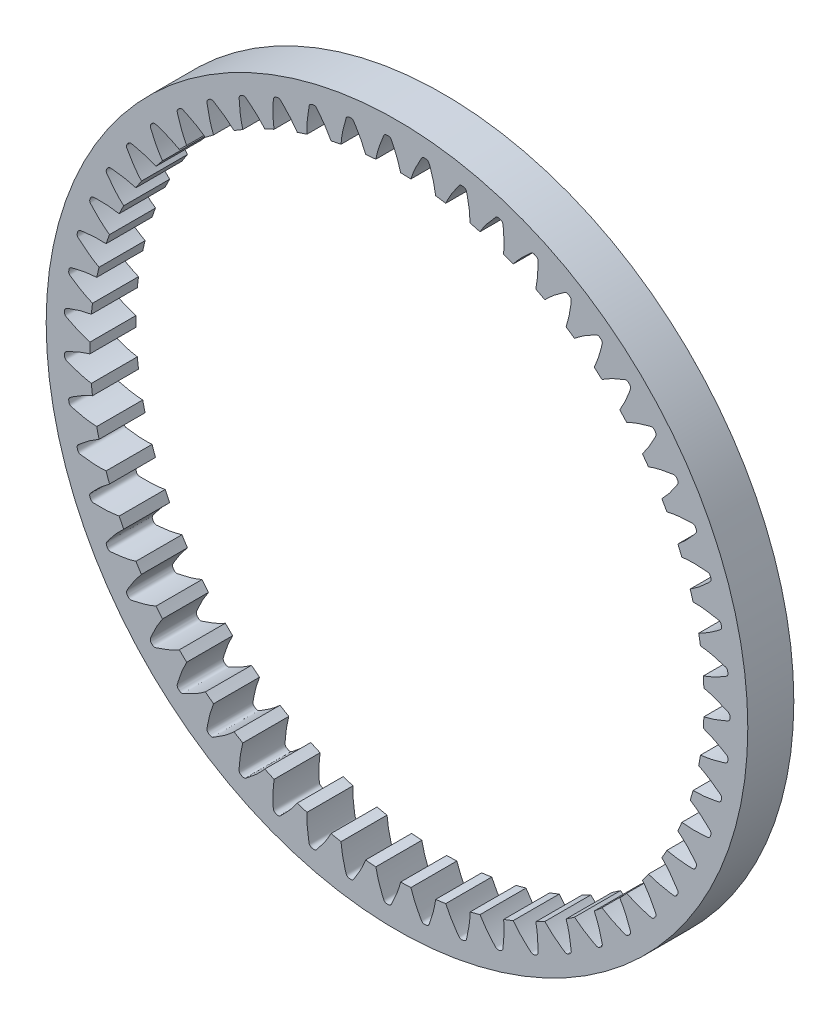
SolidWorks part; units mm, degrees
ref_plane "Front Plane" through (0, 0, 0) normal (0, 0, 1) x (1, 0, 0)
ref_plane "Top Plane" through (0, 0, 0) normal (0, 1, 0) x (1, 0, 0)
ref_plane "Right Plane" through (0, 0, 0) normal (1, 0, 0) x (0, 0, -1)
ref_axis "Axis1" through (0, 0, 55) along (0, 0, -1)
sketch "SketchRevolveSpurGear" plane through (0, 0, 0) normal (1, 0, 0) x (0, 0, -1)
  line L0 (0, 0) -> (1, 0) construction
  line L1 (-2, 26.7) -> (-2, 31.5)
  line L2 (-2, 31.5) -> (2, 31.5)
  line L3 (2, 31.5) -> (2, 26.7)
  line L4 (2, 26.7) -> (-2, 26.7)
  dimension "Side1" = 2
  dimension "OutsideRadius" = 31.5
  dimension "Side2" = 2
  dimension "MinorDiameter" = 53.4
revolve "SpurGear" add sketch "SketchRevolveSpurGear" angle 360 about L0
sketch "SketchToothSpurGear" plane through (0, 0, 0) normal (0, 0, 1) x (1, 0, 0)
  arc A0 (26.6611, -1.0844) -> (26.6611, 1.0844) centre (0, 0) ccw
  spline S0 degree 3 poles (26.6611, 1.0844) (26.7713, 1.0607) (26.9424, 1.0195) (27.1776, 0.9545) (27.373, 0.8955) (27.5803, 0.8276) (27.7992, 0.7503) (28.0292, 0.6628) (28.2705, 0.5652) (28.5213, 0.4543) (28.7068, 0.3744) (28.8169, 0.3155) (28.8506, 0.2891) (28.8801, 0.2588) (28.905, 0.2247) (28.9248, 0.1873) (28.9441, 0.1349) (28.9506, 0.0821) (28.9499, 0.0327) (28.9501, 0) (28.9499, -0.0327) (28.9506, -0.0821) (28.9441, -0.1349) (28.9248, -0.1873) (28.905, -0.2247) (28.8801, -0.2588) (28.8506, -0.2891) (28.8169, -0.3155) (28.7068, -0.3744) (28.5213, -0.4543) (28.2705, -0.5652) (28.0292, -0.6628) (27.7992, -0.7503) (27.5803, -0.8276) (27.373, -0.8955) (27.1776, -0.9545) (26.9424, -1.0195) (26.7713, -1.0607) (26.6611, -1.0844) knots 0 0 0 0 0.063683 0.099491 0.137943 0.17904 0.222781 0.269167 0.318197 0.369871 0.42419 0.432384 0.440322 0.448261 0.456199 0.464138 0.472077 0.487661 0.493831 0.5 0.506169 0.512339 0.527923 0.535862 0.543801 0.551739 0.559678 0.567616 0.57581 0.630129 0.681803 0.730833 0.777219 0.82096 0.862057 0.900509 0.936317 1 1 1 1
extrude "ToothExtrudeCutSpurGear" cut sketch "SketchToothSpurGear" against normal blind 2 and the other way blind 2
pattern_circular "PatternSpurGear" count 55 every 6.545 about axis through (0, 0, 55) along (0, 0, -1) of "ToothExtrudeCutSpurGear"
sketch "AuxiliarySketchSpurGear" plane through (0, 0, 0) normal (0, 0, 1) x (1, 0, 0)
  circle A0 centre (0, 0) radius 27.5 construction
  circle A1 centre (0, 0) radius 25.8415 construction
  circle A2 centre (0, 0) radius 28.95 construction
  circle A3 centre (0, 0) radius 26.7 construction
  dimension "PitchDiameter" = 55
  dimension "BaseDiameter" = 51.6831
  dimension "MajorDiameter" = 57.9
  dimension "MinorDiameter" = 53.4
sketch "Sketch4" plane through (0, 0, 0) normal (0, 0, 1) x (1, 0, 0)
  circle A0 centre (0, 0) radius 30.5
  circle A1 centre (0, 0) radius 59.7587
  dimension "D1" = 61
extrude "Cut-Extrude2" cut sketch "Sketch4" against normal through all both and the other way through all
